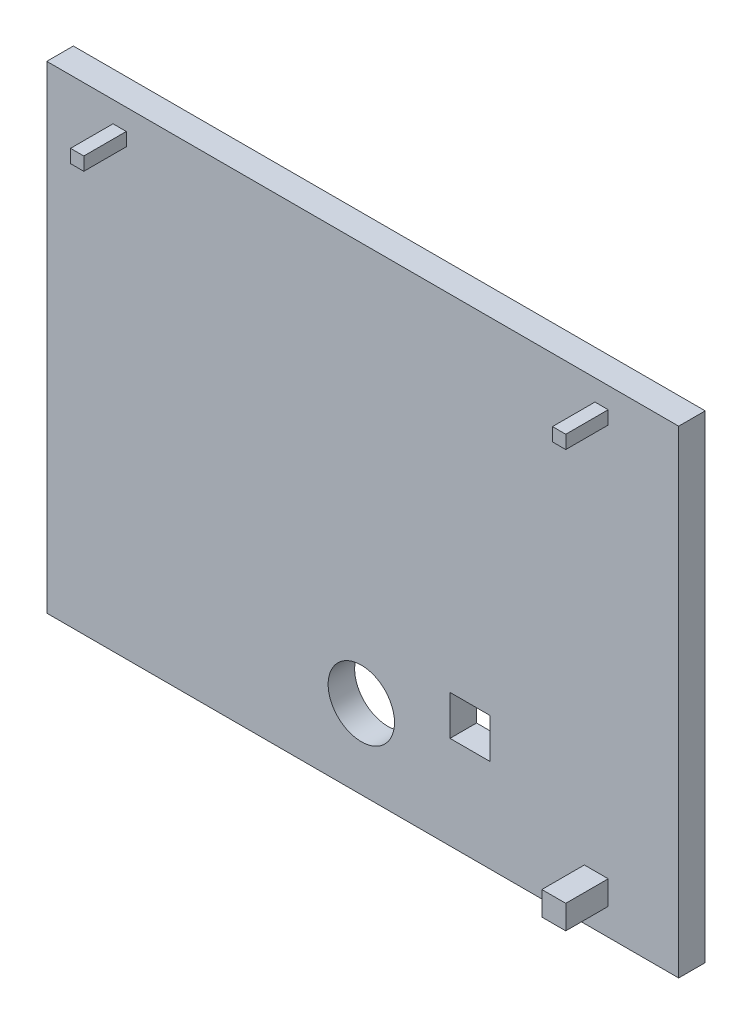
SolidWorks part; units mm, degrees
ref_plane "Front Plane" through (0, 0, 0) normal (0, 0, 1) x (1, 0, 0)
ref_plane "Top Plane" through (0, 0, 0) normal (0, 1, 0) x (1, 0, 0)
ref_plane "Right Plane" through (0, 0, 0) normal (1, 0, 0) x (0, 0, -1)
sketch "Sketch1" plane through (0, 0, 0) normal (0, 0, 1) x (1, 0, 0)
  line L1 (-15.2801, -40.9528) -> (83.7099, -40.9528)
  line L2 (-15.2801, -40.9528) -> (-15.2801, -126.2128)
  line L3 (-15.2801, -126.2128) -> (83.7099, -126.2128)
  line L4 (83.7099, -40.9528) -> (83.7099, -126.2128)
  line L17 (-12.8101, -42.5328) -> (-10.3101, -42.5328)
  line L18 (-12.8101, -42.5328) -> (-12.8101, -45.0328)
  line L19 (-12.8101, -45.0328) -> (-10.3101, -45.0328)
  line L20 (-10.3101, -42.5328) -> (-10.3101, -45.0328)
  line L21 (77.9499, -42.5328) -> (80.4499, -42.5328)
  line L22 (77.9499, -42.5328) -> (77.9499, -45.0328)
  line L23 (77.9499, -45.0328) -> (80.4499, -45.0328)
  line L24 (80.4499, -42.5328) -> (80.4499, -45.0328)
  line L25 (80.4499, -123.5328) -> (75.9499, -123.5328)
  line L26 (80.4499, -123.5328) -> (80.4499, -119.0328)
  line L27 (80.4499, -119.0328) -> (75.9499, -119.0328)
  line L28 (75.9499, -123.5328) -> (75.9499, -119.0328)
  line L29 (50.6499, -103.5328) -> (58.1499, -103.5328)
  line L30 (50.6499, -103.5328) -> (50.6499, -111.0328)
  line L31 (50.6499, -111.0328) -> (58.1499, -111.0328)
  line L32 (58.1499, -103.5328) -> (58.1499, -111.0328)
  line L33 (-25.2851, -38.5828) -> (93.7149, -38.5828)
  line L34 (-25.2851, -38.5828) -> (-25.2851, -128.5828)
  line L35 (-25.2851, -128.5828) -> (93.7149, -128.5828)
  line L36 (93.7149, -38.5828) -> (93.7149, -128.5828)
  circle A0 centre (33.9499, -113.6828) radius 6.25
  point P16 (80.4499, -43.7828)
  point P23 (34.2099, -35.2128)
  dimension "D15" = 12.5
  dimension "D17" = 5.35
  dimension "D20" = 7.5
  dimension "D1" = 2.5
  dimension "D2" = 2.5
  dimension "D3" = 2.5
  dimension "D4" = 2.5
  dimension "D5" = 4.5
  dimension "D6" = 4.5
  dimension "D7" = 88.26
  dimension "D8" = 3.26
  dimension "D9" = 2.47
  dimension "D10" = 1.58
  dimension "D11" = 2.68
  dimension "D12" = 3.26
  dimension "D13" = 1.58
  dimension "D14" = 74
  dimension "D16" = 42
  dimension "D18" = 8
  dimension "D19" = 17.8
  dimension "D21" = 7.5
  dimension "D22" = 44.52
  dimension "D23" = 119
  dimension "D24" = 10.005
  dimension "D25" = 10.005
  dimension "D26" = 90
  dimension "D27" = 2.37
  dimension "D28" = 2.37
extrude "Boss-Extrude1" add sketch "Sketch1" along normal blind 5 contours L4 L1 L2 L3 L17 L20 L19 L18 L21 L24 L23 L22 L25 L28 L27 L26 | L24 L21 L22 L23 | L28 L25 L26 L27 | L36 L33 L34 L35 L1 L4 L3 L2 | L17 L20 L19 L18 region at (33.9732, -82.9396, 0) region at (79.1999, -43.7828, 0) region at (78.1999, -121.2828, 0) region at (34.2149, -40.0749, 0)
extrude "Boss-Extrude2" add sketch "Sketch1<3>" along normal blind 13 contours L28 L25 L26 L27 | L19 L20 L17 L18 | L21 L24 L23 L22 region at (78.1999, -121.2828, 0)
sketch "Sketch1<3>" plane through (0, 0, 0) normal (0, 0, 1) x (1, 0, 0) same geometry as "Sketch1"
